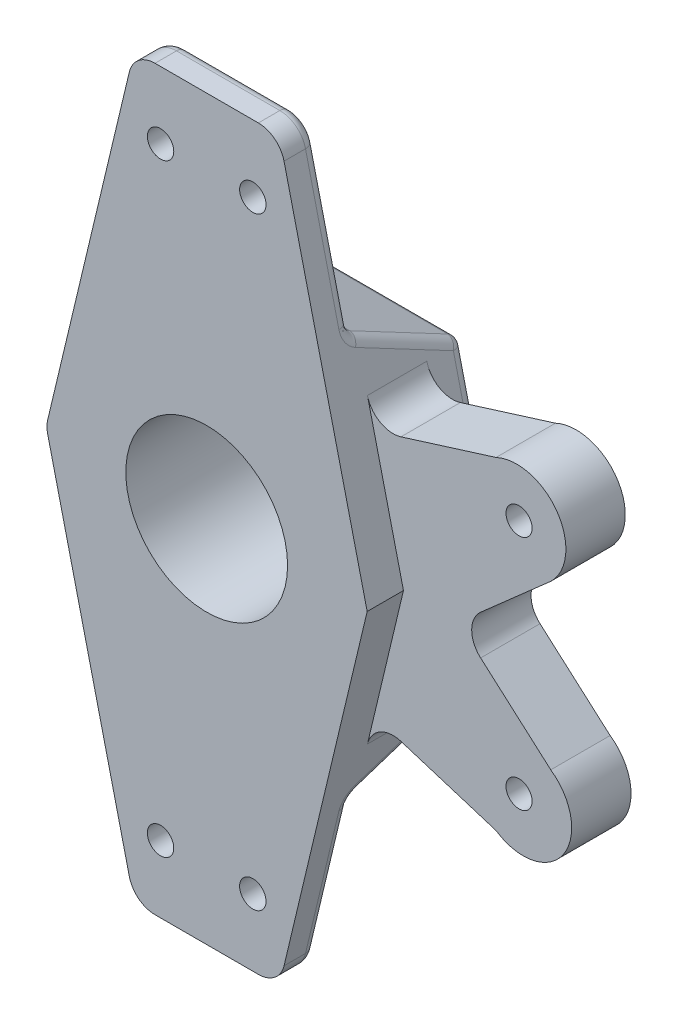
SolidWorks part; units mm, degrees
material "AISI 4340 Steel, normalized"
ref_plane "Front Plane" through (0, 0, 0) normal (0, 0, 1) x (1, 0, 0)
ref_plane "Top Plane" through (0, 0, 0) normal (0, 1, 0) x (1, 0, 0)
ref_plane "Right Plane" through (0, 0, 0) normal (1, 0, 0) x (0, 0, -1)
sketch "Sketch1" plane through (0, 0, 0) normal (0, 0, 1) x (1, 0, 0)
  line L0 (-27.4729, 139.7) -> (27.4729, 139.7)
  line L1 (27.4729, 139.7) -> (60.8037, 0)
  line L2 (60.8037, 0) -> (27.4729, -139.7)
  line L3 (27.4729, -139.7) -> (-27.4729, -139.7)
  line L4 (-27.4729, -139.7) -> (-60.8037, 0)
  line L5 (-60.8037, 0) -> (-27.4729, 139.7)
  line L6 (-60.8037, 0) -> (60.8037, 0) construction
  line L7 (0, -10.133) -> (0, 30.7361) construction
  circle A0 centre (0, 0) radius 30.65
  circle A1 centre (-17.4774, 114.3) radius 5
  circle A2 centre (17.4774, 114.3) radius 5
  circle A3 centre (17.4774, -114.3) radius 5
  circle A4 centre (-17.4774, -114.3) radius 5
  dimension "D3" = 61.3
  dimension "D4" = 10
  dimension "D5" = 139.7
  dimension "D6" = 25.4
  dimension "D7" = 34.9548
  dimension "D8" = 27.4729
  dimension "D9" = 60.8037
extrude "Boss-Extrude1" add sketch "Sketch1" along normal mid plane 50
fillet "Fillet2" radius 10 5 edges at (27.4729, -139.7, 0) (-27.4729, -139.7, 0) (27.4729, 139.7, 0) (-27.4729, 139.7, 0) (-60.8037, 0, 0)
sketch "Sketch3" plane through (0, 0, 0) normal (1, 0, 0) x (0, 0, -1)
  line L0 (-12.8655, 139.7) -> (-12.8655, 75.5)
  line L1 (-12.8655, 75.5) -> (25, 57.5)
  line L2 (32.7173, 0) -> (17.2827, 0) construction
  line L3 (-12.8655, 139.7) -> (25, 139.7)
  line L4 (25, 139.7) -> (25, 57.5)
  line L5 (25, -139.7) -> (25, -57.5)
  line L6 (-12.8655, -139.7) -> (25, -139.7)
  line L7 (-12.8655, -139.7) -> (-12.8655, -75.5)
  line L8 (-12.8655, -75.5) -> (25, -57.5)
  line L9 (25, 139.7) -> (-25, 139.7) construction
  line L11 (25, 30.8676) -> (25, -24.8837) construction
  point P8 (25, 0)
  dimension "D1" = 18
  dimension "D3" = 57.5
  dimension "D4" = 37.8655
extrude "Cut-Extrude1" cut sketch "Sketch3" against normal through all both and the other way through all
fillet "Fillet3" radius 4 23 edges at (0, 139.7, 12.8655) (0, -139.7, 12.8655) (25.7746, 137.5488, 12.8655) (-25.7746, 137.5488, 12.8655) (25.7746, -137.5488, 12.8655) (-25.7746, -137.5488, 12.8655) (36.0477, 103.7604, 12.8655) (-36.0477, 103.7604, 12.8655) (36.0477, -103.7604, 12.8655) (-36.0477, -103.7604, 12.8655) (-60.5231, 0, -25) (44.9376, 66.5, -6.0672) (-44.9376, 66.5, -6.0672) (44.9376, -66.5, -6.0672) (-44.9376, -66.5, -6.0672) (0, -75.5, 12.8655) (53.9443, 28.75, -25) (53.9443, -28.75, -25) (0, -57.5, -25) (-53.6675, -29.9104, -25) (-53.6675, 29.9104, -25) (0, 75.5, 12.8655) (0, 57.5, -25)
sketch "Sketch4" plane through (0, 0, 0) normal (0, 0, 1) x (1, 0, 0)
  line L0 (39.24, 43.5226) -> (95.87, 61.2078)
  line L1 (116.6168, 30.93) -> (81.53, 0)
  line L2 (39.24, -43.5226) -> (39.24, 43.5226)
  line L3 (116.6168, -30.93) -> (81.53, 0)
  line L4 (39.24, -43.5226) -> (95.87, -61.2078)
  circle A0 centre (104.6, 44.8) radius 4.95
  circle A1 centre (104.6, -44.8) radius 4.95
  arc A2 (95.87, -61.2078) -> (116.6168, -30.93) centre (106.18, -46.0255) ccw
  arc A3 (95.87, 61.2078) -> (116.6168, 30.93) centre (103.7438, 44.3562) cw
  point P9 (39.24, 0)
  dimension "D1" = 9.9
  dimension "D2" = 18.3521
  dimension "D3" = 18.6004
  dimension "D4" = 39.24
  dimension "D5" = 44.8
  dimension "D6" = 44.8
  dimension "D7" = 104.6
  dimension "D8" = 81.53
  dimension "D9" = 30.93
  dimension "D10" = 44.3562
  dimension "D11" = 95.87
  dimension "D12" = 106.18
  dimension "D13" = 43.5226
extrude "Boss-Extrude3" add sketch "Sketch4" along normal mid plane 22.5
fillet "Fillet4" radius 10 5 edges at (59.5993, 0, -23.8284) (49.6445, -46.7718, 0) (81.53, 0, 0) (49.6445, 46.7718, 0) (60.8037, 0, -16.125)
